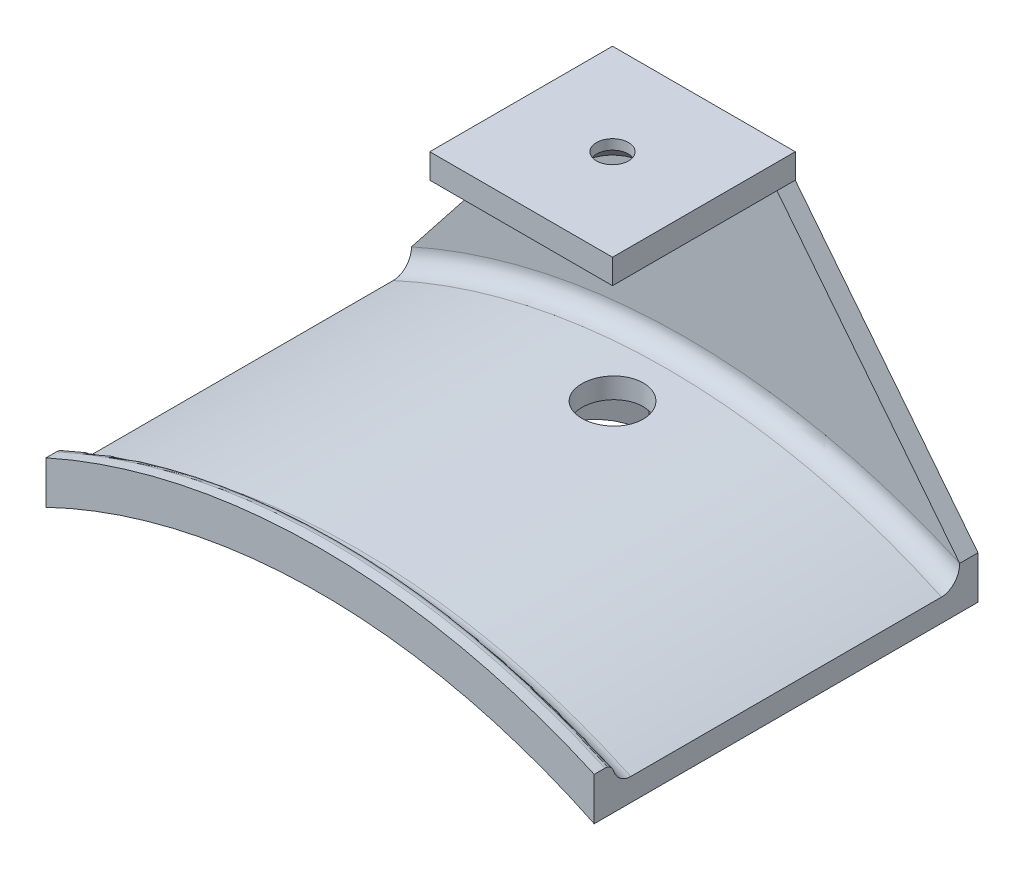
SolidWorks part; units mm, degrees
ref_plane "Alzado" through (0, 0, 0) normal (0, 0, 1) x (1, 0, 0)
ref_plane "Planta" through (0, 0, 0) normal (0, 1, 0) x (1, 0, 0)
ref_plane "Vista lateral" through (0, 0, 0) normal (1, 0, 0) x (0, 0, -1)
sketch "Croquis1" plane through (0, 0, 0) normal (0, 0, 1) x (1, 0, 0)
  line L1 (-27.252, 6.7164) -> (32.748, 6.7164)
  line L2 (-27.252, 6.7164) -> (-27.252, -23.2836)
  line L3 (-27.252, -23.2836) -> (32.748, -23.2836)
  line L4 (32.748, 6.7164) -> (32.748, -23.2836)
  dimension "D1" = 60
  dimension "D2" = 30
extrude "Saliente-Extruir1" add sketch "Croquis1" along normal blind 2
sketch "Croquis2" plane through (0, 0, 2) normal (0, 0, 1) x (1, 0, 0)
  line L0 (2.748, -23.2836) -> (2.748, -30.8244) construction
  line L1 (-27.252, -23.2836) -> (32.748, -23.2836) construction
  line L2 (44.948, -30.8244) -> (-39.452, -30.8244) construction
  line L3 (2.748, -30.8244) -> (2.748, -16.4244) construction
  line L4 (-27.252, -23.2836) -> (-27.252, -20.7945)
  line L5 (-27.252, 6.7164) -> (-27.252, -23.2836) construction
  line L6 (32.748, -23.2836) -> (32.748, -20.7945)
  line L7 (32.748, -23.2836) -> (32.748, 6.7164) construction
  arc A0 (-39.452, -30.8244) -> (44.948, -30.8244) centre (2.748, -85.4591) cw construction
  arc A1 (-27.252, -23.2836) -> (32.748, -23.2836) centre (2.748, -85.4591) cw
  arc A2 (-27.252, -20.7945) -> (32.748, -20.7945) centre (2.748, -85.4591) cw
  arc A4 (-28.2298, -21.2571) -> (33.7258, -21.2571) centre (2.748, -85.4591) cw construction
  dimension "D2" = 14.4
  dimension "D1" = 42.2
  dimension "D3" = 2.25
extrude "Saliente-Extruir2" add sketch "Croquis2" along normal blind 38
sketch "Croquis5" plane through (0, 0, 40) normal (0, 0, 1) x (1, 0, 0)
  line L0 (2.748, -16.4244) -> (2.748, -14.1744) construction
  line L1 (32.748, -23.2836) -> (32.748, -18.5962)
  line L2 (-27.252, -23.2836) -> (-27.252, -18.5962)
  arc A1 (32.748, -23.2836) -> (-27.252, -23.2836) centre (2.748, -85.4591) ccw construction
  arc A2 (-27.252, -23.2836) -> (32.748, -23.2836) centre (2.748, -85.4591) cw
  arc A3 (32.748, -20.7945) -> (-27.252, -20.7945) centre (2.748, -85.4591) ccw construction
  arc A8 (33.5897, -18.9802) -> (-28.0937, -18.9802) centre (2.748, -85.4591) ccw
  arc A9 (32.748, -18.5962) -> (-27.252, -18.5962) centre (2.748, -85.4591) ccw
  point P16 (-27.252, -17.1616)
  dimension "D1" = 2
extrude "Saliente-Extruir4" add sketch "Croquis5" along normal blind 2
fillet "Redondeo1" radius 2 2 edges at (2.748, -14.1744, 2) (2.748, -14.1744, 40)
fillet "Redondeo2" radius 1 1 edges at (2.748, -12.1744, 40)
sketch "Croquis6" plane through (0, 0, 2) normal (0, 0, 1) x (1, 0, 0)
  line L0 (-27.252, -18.5962) -> (-7.252, 6.7164)
  line L1 (32.748, 6.7164) -> (-27.252, 6.7164) construction
  line L2 (2.748, 6.7164) -> (2.748, -12.1744) construction
  line L3 (-7.252, 6.7164) -> (-27.252, 6.7164)
  line L4 (-27.252, 6.7164) -> (-27.252, -18.5962)
  line L5 (12.748, 6.7164) -> (32.748, 6.7164)
  line L6 (32.748, -18.5962) -> (12.748, 6.7164)
  line L7 (32.748, 6.7164) -> (32.748, -18.5962)
  arc A0 (32.748, -18.5962) -> (-27.252, -18.5962) centre (2.748, -85.4591) ccw construction
  dimension "D1" = 10
extrude "Cortar-Extruir2" cut sketch "Croquis6" against normal up to vertex (2 mm away) up to point (-27.252, 6.7164, 0)
sketch "Croquis7" plane through (0, 6.7164, 0) normal (0, 1, 0) x (1, 0, 0)
  line L1 (-7.252, 0) -> (12.748, 0)
  line L2 (-7.252, 0) -> (-7.252, -20)
  line L3 (-7.252, -20) -> (12.748, -20)
  line L4 (12.748, 0) -> (12.748, -20)
  dimension "D1" = 20
extrude "Saliente-Extruir5" add sketch "Croquis7" along normal blind 2.7
sketch "Croquis8" plane through (0, 9.4164, 0) normal (0, 1, 0) x (1, 0, 0)
  circle A0 centre (2.748, -10) radius 1.75
  dimension "D1" = 3.5
extrude "Cortar-Extruir3" cut sketch "Croquis8" against normal up to vertex (2.7 mm away) up to point (-7.252, 6.7164, 20)
hole_wizard "Refrentado para tornillo tapón con cabeza plana de clavija de M31" positions "Croquis9" profile "Croquis10" countersink size "M3" standard "Ansi Metric" end condition through all
sketch "Croquis9" plane through (0, 6.7164, 0) normal (0, -1, 0) x (-1, 0, 0)
  point P0 (-2.748, -10)
sketch "Croquis10" plane through (2.748, 6.7164, 10) normal (1, 0, 0) x (0, 0, -1)
  line L0 (0, 0) -> (0, 2.7)
  line L1 (0, 2.7) -> (1.7, 2.7)
  line L2 (1.7, 2.7) -> (1.7, 1.66)
  line L3 (1.7, 1.66) -> (3.36, 0)
  line L5 (3.36, 0) -> (0, 0)
  line L6 (-1.7, 1.66) -> (-3.36, 0) construction
  line L11 (0, -6.35) -> (0, 107.95) construction
  dimension "Diámetro de taladro hasta el siguiente" = 3.4
  dimension "Profundidad de taladro hasta el siguiente" = 2.7
  dimension "Diámetro de avellanado cercano" = 6.72
  dimension "Ángulo de avellanado cercano" = 90
sketch "Croquis11" plane through (0, 6.7164, 0) normal (0, -1, 0) x (1, 0, 0)
  circle A0 centre (2.748, 10) radius 3.36
extrude "Cortar-Extruir4" cut sketch "Croquis11" along normal blind 50
sketch "Croquis3" plane through (0, 0, 2) normal (0, 0, 1) x (1, 0, 0)
  line L0 (2.748, -23.2836) -> (-1.252, -23.2836) construction
  line L1 (2.748, -23.2836) -> (2.748, -16.4244) construction
  line L5 (-27.252, -23.2836) -> (32.748, -23.2836) construction
  line L6 (-1.252, -23.2836) -> (-1.252, -16.5403)
  line L7 (-1.252, -23.2836) -> (-3.502, -23.2836)
  line L8 (-3.502, -23.2836) -> (-3.502, -16.7079)
  line L9 (8.998, -23.2836) -> (8.998, -16.7079)
  line L10 (6.748, -23.2836) -> (8.998, -23.2836)
  line L11 (6.748, -23.2836) -> (6.748, -16.5403)
  arc A0 (-3.502, -16.7079) -> (-1.252, -16.5403) centre (2.748, -85.4591) cw
  arc A2 (32.748, -23.2836) -> (-27.252, -23.2836) centre (2.748, -85.4591) ccw construction
  arc A3 (8.998, -16.7079) -> (6.748, -16.5403) centre (2.748, -85.4591) ccw
  dimension "D1" = 4
extrude "Saliente-Extruir3" add sketch "Croquis3" along normal blind 15
sketch "Croquis4" plane through (-3.502, 0, 0) normal (-1, 0, 0) x (0, 0, 1)
  line L0 (17, -16.7079) -> (17, -23.2836)
  line L1 (17, -23.2836) -> (2, -23.2836)
  arc A0 (2, -23.2836) -> (17, -16.7079) centre (17.7469, -38.8079) cw
  point P3 (17, -23.2836)
  point P8 (17, -16.7079)
  point P11 (2, -23.2836)
extrude "Cortar-Extruir1" cut sketch "Croquis4" against normal up to vertex (12.5 mm away) up to point (8.998, -16.7079, 17)
